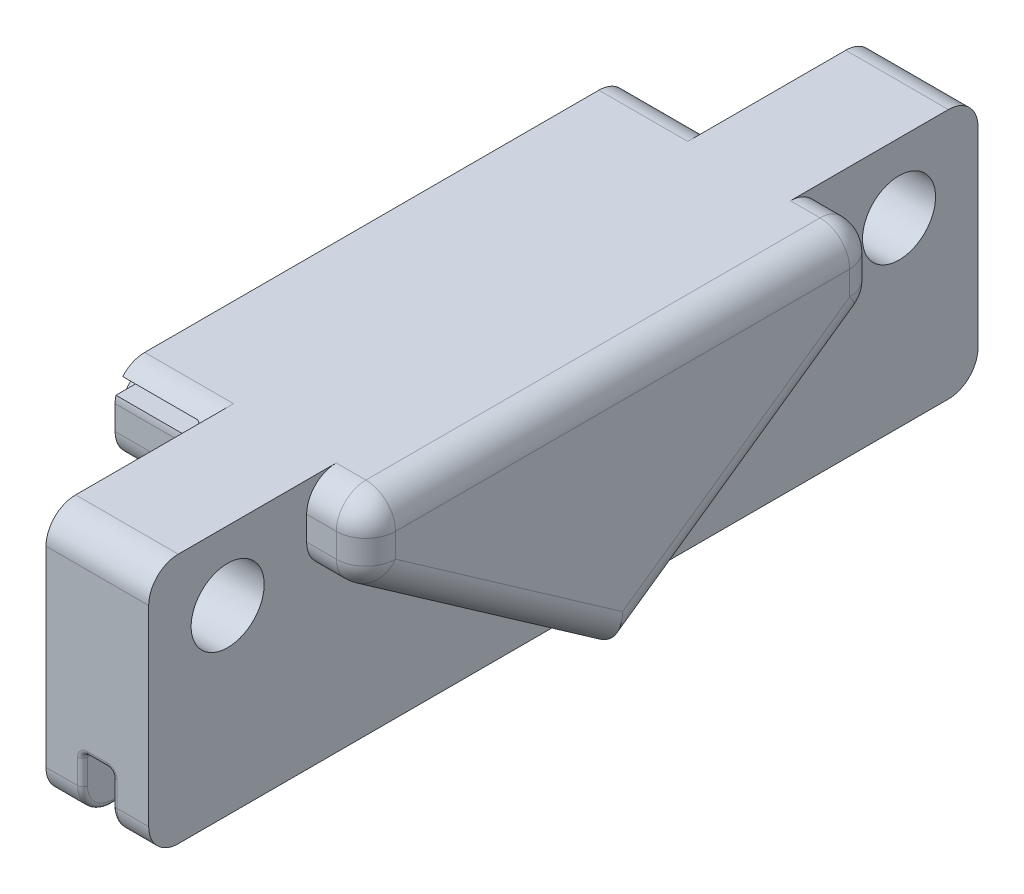
SolidWorks part; units mm, degrees
note: The reader was unsure of these and kept them because the rebuilt part matched: shared geometry of "Sketch7<4>", "Sketch7<5>", "Sketch7<6>".
ref_plane "Front Plane" through (0, 0, 0) normal (0, 0, 1) x (1, 0, 0)
ref_plane "Top Plane" through (0, 0, 0) normal (0, 1, 0) x (1, 0, 0)
ref_plane "Right Plane" through (0, 0, 0) normal (1, 0, 0) x (0, 0, -1)
sketch "Sketch1" plane through (0, 0, 0) normal (0, 1, 0) x (1, 0, 0)
  line L0 (-28.7782, 15.5442) -> (-24.2782, 15.5442)
  line L1 (-24.2782, 15.5442) -> (-24.2782, 23.5442)
  line L2 (-24.2782, 23.5442) -> (-19.0782, 23.5442)
  line L3 (-19.0782, 23.5442) -> (-19.0782, 15.5442)
  line L4 (-19.0782, 15.5442) -> (-16.0782, 15.5442)
  line L5 (-16.0782, 15.5442) -> (-16.0782, 2.5442)
  line L7 (-16.0782, 2.5442) -> (-28.7782, 2.5442)
  line L9 (-28.7782, 2.5442) -> (-28.7782, 15.5442)
  dimension "D1" = 12.7
  dimension "D2" = 3
  dimension "D3" = 8
  dimension "D4" = 13
extrude "Boss-Extrude1" add sketch "Sketch1" along normal blind 12.7
sketch "Sketch7" plane through (-28.7782, 0, 0) normal (-1, 0, 0) x (0, 0, 1)
  line L0 (-15.5442, 12.7) -> (-15.5442, -1.2986) construction
  line L5 (-15.5442, 12.7) -> (-15.5442, 9.2)
  line L6 (-12.2942, 12.0986) -> (-12.2942, 6.3014) construction
  line L7 (-12.2942, 9.2) -> (-15.8582, 9.2) construction
  line L8 (-15.5442, 9.2) -> (-2.5442, 0.0973)
  line L9 (-2.5442, 0.0973) -> (-2.5442, 12.7)
  line L10 (-2.5442, 12.7) -> (-15.5442, 12.7)
  line L11 (-2.5442, 12.2) -> (-15.5442, 12.2)
  line L12 (-15.5442, 12.2) -> (-15.5442, 11.55)
  line L13 (-15.5442, 9.2) -> (-15.5442, 0)
  line L14 (-15.5442, 11.55) -> (-2.5442, 11.55)
  line L15 (-2.5442, 11.55) -> (-2.5442, 12.2)
  line L16 (-15.5442, 0) -> (-2.5442, 0)
  line L17 (-2.5442, 0) -> (-2.5442, 0.0973)
  line L18 (-2.5442, 0.0973) -> (-15.5442, 9.2)
  line L19 (-15.5442, 0) -> (-15.5442, 9.2)
  line L20 (-15.5442, 9.2) -> (-23.5442, 9.2) construction
  line L22 (-2.5442, 12.7) -> (-15.5442, 12.7) construction
  line L23 (-19.5442, 12.7) -> (-19.5442, 0) construction
  line L24 (-23.5442, 12.7) -> (-15.5442, 12.7) construction
  line L25 (-23.5442, 0) -> (-15.5442, 0) construction
  line L26 (-23.5442, 12.7) -> (-23.5442, 0) construction
  circle A0 centre (-12.2942, 9.2) radius 1.6
  circle A1 centre (-19.5442, 9.2) radius 1.85
  line M20 (-15.5442, 0) -> (-2.5442, 0)
  line M21 (-2.5442, 0) -> (-2.5442, 12.7)
  line M23 (-15.5442, 12.7) -> (-15.5442, 0)
  dimension "D2" = 0.5
  dimension "D4" = 3.5
  dimension "D5" = 3.25
  dimension "D6" = 0.65
  dimension "D7" = 3.5
  dimension "D8" = 4
extrude "Cut-Extrude2" cut sketch "Sketch7" against normal blind 4 contours L15 L11 L12 L14
extrude "Boss-Extrude2" add sketch "Sketch7<4>" along normal blind 1.4 contours A0
sketch "Sketch7<4>" plane through (-28.7782, 0, 0) normal (-1, 0, 0) x (0, 0, 1) same geometry as "Sketch7"
extrude "Cut-Extrude3" cut sketch "Sketch7<5>" against normal up to surface (4.5 mm away) contours L8 M23 M20 M21 up to face at (-24.2782, 6.35, -19.5442)
sketch "Sketch7<5>" plane through (-28.7782, 0, 0) normal (-1, 0, 0) x (0, 0, 1) same geometry as "Sketch7"
extrude "Cut-Extrude4" cut sketch "Sketch7<6>" against normal through all and the other way through all contours A1
sketch "Sketch7<6>" plane through (-28.7782, 0, 0) normal (-1, 0, 0) x (0, 0, 1) same geometry as "Sketch7"
sketch "Sketch10" plane through (-19.0782, 0, 0) normal (1, 0, 0) x (0, 0, -1)
  line L1 (15.5442, 9.2) -> (15.5442, 0)
  line L3 (15.5442, 0) -> (2.5442, 0)
  line L4 (2.5442, 0) -> (2.5442, 0.0973)
  line L7 (2.5442, 0.0973) -> (15.5442, 9.2)
  dimension "D1" = 13
  dimension "D2" = 9.2
extrude "Cut-Extrude5" cut sketch "Sketch10" along normal up to surface (3 mm away) from surface
sketch "Sketch12" plane through (0, 0, 0) normal (0, -1, 0) x (1, 0, 0)
  line L0 (-21.6782, -23.5442) -> (-21.6782, -2.5435) construction
  line L3 (-19.0782, -23.5442) -> (-24.2782, -23.5442) construction
  line L8 (-19.0782, -13.0442) -> (-24.2782, -13.0442) construction
  line L9 (-19.0782, -2.5442) -> (-19.0782, -23.5442) construction
  line L10 (-24.2782, -23.5442) -> (-24.2782, -2.5442) construction
  line L12 (-22.4282, -2.5435) -> (-20.9282, -2.5435)
  line L13 (-22.4282, -2.5435) -> (-22.4282, -23.5442)
  line L14 (-22.4282, -23.5442) -> (-20.9282, -23.5442)
  line L15 (-20.9282, -2.5435) -> (-20.9282, -23.5442)
  line L16 (-22.4282, -2.5435) -> (-20.9282, -23.5442) construction
  line L17 (-22.4282, -23.5442) -> (-20.9282, -2.5435) construction
  point P6 (-21.6782, -2.5435)
  point P11 (-21.6782, -13.0439)
  dimension "D1" = 0.75
extrude "Cut-Extrude6" cut sketch "Sketch12" against normal blind 3
sketch "Sketch14" plane through (0, 0, 0) normal (0, -1, 0) x (-1, 0, 0)
  line L1 (24.2782, 2.5442) -> (19.0782, 2.5442)
  line L2 (24.2782, 2.5442) -> (24.2782, 6.5442)
  line L3 (24.2782, 6.5442) -> (19.0782, 6.5442)
  line L4 (19.0782, 2.5442) -> (19.0782, 6.5442)
  line L5 (24.2782, 23.5442) -> (24.2782, 2.5442) construction
  line L6 (19.0782, 15.5442) -> (19.0782, 2.5442) construction
  dimension "D1" = 4
extrude "Boss-Extrude3" add sketch "Sketch14" against normal blind 1
fillet "Fillet3" radius 1.5 10 edges at (-26.5282, 9.2, -15.5442) (-17.5782, 9.2, -15.5442) (-26.5282, 12.7, -15.5442) (-17.5782, 12.7, -15.5442) (-16.0782, 4.6487, -9.0442) (-16.0782, 10.95, -15.5442) (-16.0782, 12.7, -9.0442) (-21.6782, 12.7, -23.5442) (-23.3532, 0, -23.5442) (-20.0032, 0, -23.5442)
mirror "Mirror3" about plane through (-16.0782, 12.7, -2.5442) normal (0, 0, -1) of bodies 110
fillet "Fillet4" radius 0.25 28 edges at (-22.4282, 0, -14.2942) (-22.4282, 1, -2.5442) (-22.4282, 0.5, -6.5442) (-21.6782, 1, -6.5442) (-20.9282, 0.5, -6.5442) (-20.9282, 1, -2.5442) (-21.6782, 0, -6.5442) (-20.9282, 0, -14.2942) (-22.4282, 0.4393, -23.1049) (-20.9282, 0.4393, -23.1049) (-24.7782, 11.55, -2.5442) (-21.6782, 3, 18.4558) (-20.9282, 2.25, 18.4558) (-20.9282, 0, 9.2058) (-22.4282, 0, 9.2058) (-22.4282, 2.25, 18.4558) (-20.9282, 0.5, 1.4558) (-22.4282, 0.5, 1.4558) (-21.6782, 0, 1.4558) (-21.6782, 1, 1.4558) (-22.4282, 0.4393, 18.0165) (-20.9282, 0.4393, 18.0165) (-24.7782, 12.2, -2.5442) (-20.9282, 3, -2.5442) (-22.4282, 3, -2.5442) (-22.4282, 2.25, -23.5442) (-21.6782, 3, -23.5442) (-20.9282, 2.25, -23.5442)
